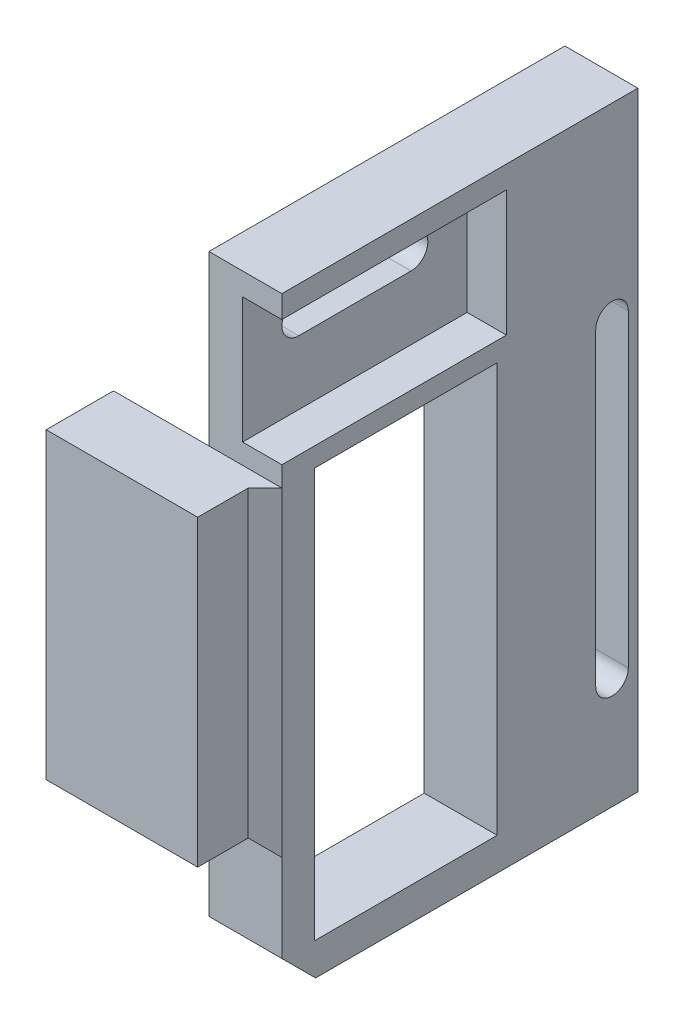
SolidWorks part; units mm, degrees
ref_plane "前视基准面" through (0, 0, 0) normal (0, 0, 1) x (1, 0, 0)
ref_plane "上视基准面" through (0, 0, 0) normal (0, 1, 0) x (1, 0, 0)
ref_plane "右视基准面" through (0, 0, 0) normal (1, 0, 0) x (0, 0, -1)
other "Configuration Table"
sketch "草图1" plane through (0, 0, 0) normal (1, 0, 0) x (0, 0, -1)
  line L0 (-13.55, 21.15) -> (13.55, 21.15)
  line L1 (-10.55, -18.15) -> (10.55, -18.15)
  line L2 (-10.55, -18.15) -> (-10.55, 18.15)
  line L3 (-10.55, 18.15) -> (10.55, 18.15)
  line L4 (10.55, -18.15) -> (10.55, 18.15)
  line L5 (-10.55, -18.15) -> (10.55, 18.15) construction
  line L6 (-10.55, 18.15) -> (10.55, -18.15) construction
  line L7 (13.55, -21.15) -> (13.55, 21.15)
  line L8 (-13.55, -21.15) -> (13.55, -21.15)
  line L9 (-13.55, -21.15) -> (-13.55, 21.15)
  point P0 (0, 0)
  dimension "D1" = 36.3
  dimension "D2" = 21.1
  dimension "D3" = 3
extrude "凸台-拉伸1" add sketch "草图1" along normal blind 6.5
chamfer "倒角1" distance 3 angle 45 4 edges at (3.25, -21.15, 13.55) (3.25, 21.15, 13.55) (3.25, 21.15, -13.55) (3.25, -21.15, -13.55)
sketch "草图2" plane through (0, 0, 0) normal (-1, 0, 0) x (0, 0, 1)
  line L0 (13.55, 18.15) -> (13.55, -18.15) construction
  line L1 (13.55, 12.15) -> (18.55, 12.15)
  line L2 (13.55, 12.15) -> (13.55, -12.15)
  line L3 (13.55, -12.15) -> (18.55, -12.15)
  line L4 (18.55, 12.15) -> (18.55, -12.15)
  line L5 (10.55, -18.15) -> (-10.55, -18.15) construction
  line L6 (-10.55, 18.15) -> (10.55, 18.15) construction
  circle A0 centre (16.05, 7.15) radius 1.475
  circle A1 centre (16.05, -7.15) radius 1.475
  dimension "D4" = 2.5
  dimension "D6" = 2.95
  dimension "D8" = 2.95
  dimension "D1" = 6
  dimension "D2" = 6
  dimension "D3" = 5
  dimension "D5" = 5
  dimension "D7" = 5
  dimension "D9" = 2.5
extrude "凸台-拉伸2" add sketch "草图2" along normal blind 8.7 and the other way blind 6.5
sketch "草图3" plane through (6.5, 0, 0) normal (1, 0, 0) x (0, 0, -1)
  line L0 (-13.55, 18.15) -> (-13.55, 12.15) construction
  line L1 (13.55, 18.15) -> (-13.55, 18.15)
  line L2 (13.55, 18.15) -> (13.55, 33.15)
  line L3 (13.55, 33.15) -> (-13.55, 33.15)
  line L4 (-13.55, 18.15) -> (-13.55, 33.15)
  dimension "D1" = 15
extrude "凸台-拉伸3" add sketch "草图3" against normal blind 6.5
sketch "草图4" plane through (0, 0, 0) normal (-1, 0, 0) x (0, 0, 1)
  line L0 (-10.55, 18.15) -> (10.55, 18.15) construction
  line L1 (-13.55, 33.15) -> (-31.1578, 33.15)
  line L2 (-13.55, 33.15) -> (-13.55, 18.15)
  line L3 (-13.55, 18.15) -> (-31.1578, 18.15)
  line L4 (-31.1578, 33.15) -> (-31.1578, 18.15)
extrude "凸台-拉伸4" add sketch "草图4" against normal blind 6.5
sketch "草图5" plane through (0, 0, 0) normal (-1, 0, 0) x (0, 0, 1)
  line L0 (13.55, 33.15) -> (13.55, 12.15) construction
  line L1 (13.55, 31.2141) -> (-6.45, 31.2141)
  line L2 (13.55, 31.2141) -> (13.55, 20.2141)
  line L3 (13.55, 20.2141) -> (-6.45, 20.2141)
  line L4 (-6.45, 31.2141) -> (-6.45, 20.2141)
  line L5 (10.55, -18.15) -> (-10.55, -18.15) construction
  line L6 (-10.55, 18.15) -> (-5.55, 18.15)
  line L7 (-10.55, 18.15) -> (-10.55, -18.15)
  line L8 (-10.55, -18.15) -> (-5.55, -18.15)
  line L9 (-5.55, 18.15) -> (-5.55, -18.15)
  line L10 (10.55, 18.15) -> (10.55, -18.15) construction
  dimension "D1" = 11
  dimension "D2" = 20
  dimension "D3" = 16.1
extrude "凸台-拉伸5" add sketch "草图5" against normal blind 6.5
sketch "草图6" plane through (0, 0, 0) normal (-1, 0, 0) x (0, 0, 1)
  line L0 (13.55, 33.15) -> (13.55, 12.15) construction
  line L1 (13.55, 31.15) -> (-6.45, 31.15)
  line L2 (13.55, 31.15) -> (13.55, 19.95)
  line L3 (13.55, 19.95) -> (-6.45, 19.95)
  line L4 (-6.45, 31.15) -> (-6.45, 19.95)
  line L5 (-31.1578, 33.15) -> (13.55, 33.15) construction
  dimension "D1" = 20
  dimension "D2" = 11.2
  dimension "D3" = 2
extrude "切除-拉伸5" cut sketch "草图6" against normal through all both
sketch "草图9" plane through (-8.7, 0, 0) normal (-1, 0, 0) x (0, 0, 1)
  line L4 (13.55, 12.15) -> (13.55, -12.15)
  line L5 (13.55, -12.15) -> (18.55, -12.15)
  line L6 (18.55, -12.15) -> (18.55, 12.15)
  line L7 (18.55, 12.15) -> (13.55, 12.15)
  line L8 (13.55, 12.15) -> (13.55, -12.15)
  line L9 (13.55, -12.15) -> (18.55, -12.15)
  line L10 (18.55, -12.15) -> (18.55, 12.15)
  line L11 (18.55, 12.15) -> (13.55, 12.15)
  dimension "D1" = 0
extrude "切除-拉伸6" cut sketch "草图9" against normal through all both
sketch "草图10" plane through (0, 0, 0) normal (-1, 0, 0) x (0, 0, 1)
  line L1 (13.55, 31.15) -> (-6.45, 31.15)
  line L2 (13.55, 31.15) -> (13.55, 19.95)
  line L3 (13.55, 19.95) -> (-6.45, 19.95)
  line L4 (-6.45, 31.15) -> (-6.45, 19.95)
extrude "凸台-拉伸6" add sketch "草图10" against normal blind 3
sketch "草图11" plane through (6.5, 0, 0) normal (1, 0, 0) x (0, 0, -1)
  line L0 (31.1578, 18.15) -> (13.55, 18.15) construction
  line L1 (31.1578, 33.15) -> (18.1578, 33.15)
  line L2 (31.1578, 33.15) -> (31.1578, 18.15)
  line L3 (31.1578, 18.15) -> (18.1578, 18.15)
  line L4 (18.1578, 33.15) -> (18.1578, 18.15)
  dimension "D1" = 13
extrude "切除-拉伸7" cut sketch "草图11" against normal through all both and the other way through all
sketch "草图13" plane through (0, 0, 0) normal (-1, 0, 0) x (0, 0, 1)
  line L0 (13.55, 33.15) -> (13.55, -18.15) construction
  line L1 (13.55, 18.15) -> (19.55, 18.15)
  line L2 (13.55, 18.15) -> (13.55, -8.85)
  line L3 (13.55, -8.85) -> (19.55, -8.85)
  line L4 (19.55, 18.15) -> (19.55, -8.85)
  line L5 (-5.55, 18.15) -> (10.55, 18.15) construction
  dimension "D1" = 6
  dimension "D2" = 27
  dimension "D3" = 0
extrude "凸台-拉伸7" add sketch "草图13" along normal blind 8.5 and the other way blind 5
chamfer "倒角2" distance 1.5 angle 45 2 edges at (5, 4.65, 13.55) (2.5, -8.85, 13.55)
sketch "草图14" plane through (0, 0, 0) normal (-1, 0, 0) x (0, 0, 1)
  line L0 (10.63, 18.23) -> (-5.63, 18.23)
  line L1 (-5.63, 18.23) -> (-5.63, -18.23)
  line L2 (-5.63, -18.23) -> (10.63, -18.23)
  line L3 (10.63, -18.23) -> (10.63, 18.23)
  line L4 (-5.55, 18.15) -> (-5.55, -18.15)
  line L5 (10.55, 18.15) -> (-5.55, 18.15)
  line L6 (10.55, -18.15) -> (10.55, 18.15)
  line L7 (-5.55, -18.15) -> (10.55, -18.15)
  line L8 (-5.55, 18.15) -> (-5.55, -18.15)
  line L9 (10.55, 18.15) -> (-5.55, 18.15)
  line L10 (10.55, -18.15) -> (10.55, 18.15)
  line L11 (-5.55, -18.15) -> (10.55, -18.15)
  dimension "D1" = 0
  dimension "D2" = 0.08
extrude "切除-拉伸8" cut sketch "草图14" against normal through all
sketch "草图15" plane through (6.5, 0, 0) normal (1, 0, 0) x (0, 0, -1)
  line L1 (18.1578, 18.15) -> (10.55, 18.15)
  line L2 (18.1578, 18.15) -> (18.1578, -21.15)
  line L3 (18.1578, -21.15) -> (10.55, -21.15)
  line L4 (10.55, 18.15) -> (10.55, -21.15)
extrude "凸台-拉伸8" add sketch "草图15" against normal blind 6
sketch "草图16" plane through (3, 0, 0) normal (1, 0, 0) x (0, 0, -1)
  line L0 (-8.55, 27.15) -> (1.45, 27.15) construction
  line L1 (-8.55, 28.65) -> (1.45, 28.65)
  line L2 (-8.55, 25.65) -> (1.45, 25.65)
  line L3 (6.45, 31.15) -> (6.45, 19.95) construction
  line L4 (-13.55, 31.15) -> (6.45, 31.15) construction
  arc A0 (-8.55, 28.65) -> (-8.55, 25.65) centre (-8.55, 27.15) ccw
  arc A1 (1.45, 25.65) -> (1.45, 28.65) centre (1.45, 27.15) ccw
  point P2 (-3.55, 27.15)
  dimension "D4" = 1.5
  dimension "D1" = 10
  dimension "D2" = 5
  dimension "D3" = 4
extrude "切除-拉伸9" cut sketch "草图16" against normal blind 6
sketch "草图17" plane through (0.5, 0, 0) normal (-1, 0, 0) x (0, 0, 1)
  line L5 (-13.55, -18.15) -> (-13.55, 18.15)
  line L6 (-13.55, 18.15) -> (-18.1578, 18.15)
  line L7 (-18.1578, 18.15) -> (-18.1578, -21.15)
  line L8 (-18.1578, -21.15) -> (-10.55, -21.15)
  line L9 (-10.55, -21.15) -> (-13.55, -18.15)
  line L10 (-13.55, -18.15) -> (-13.55, 18.15)
  line L11 (-13.55, 18.15) -> (-18.1578, 18.15)
  line L12 (-18.1578, 18.15) -> (-18.1578, -21.15)
  line L13 (-18.1578, -21.15) -> (-10.55, -21.15)
  line L14 (-10.55, -21.15) -> (-13.55, -18.15)
  dimension "D1" = 0
extrude "凸台-拉伸9" add sketch "草图17" along normal blind 0.5
sketch "草图18" plane through (0, 0, 0) normal (-1, 0, 0) x (0, 0, 1)
  line L0 (-15.8578, 11.85) -> (-15.8578, -11.15) construction
  line L1 (-14.4078, 11.85) -> (-14.4078, -11.15)
  line L2 (-17.3078, 11.85) -> (-17.3078, -11.15)
  line L3 (-18.1578, 33.15) -> (-18.1578, -21.15) construction
  line L5 (10.55, -21.15) -> (-18.1578, -21.15) construction
  arc A0 (-14.4078, 11.85) -> (-17.3078, 11.85) centre (-15.8578, 11.85) ccw
  arc A1 (-17.3078, -11.15) -> (-14.4078, -11.15) centre (-15.8578, -11.15) ccw
  point P2 (-15.8578, 0.35)
  dimension "D4" = 23
  dimension "D1" = 2.3
  dimension "D2" = 2.9
  dimension "D3" = 10
extrude "切除-拉伸10" cut sketch "草图18" against normal through all
sketch "草图19" plane through (6.5, 0, 0) normal (1, 0, 0) x (0, 0, -1)
  line L1 (14.4078, 11.85) -> (17.3078, 11.85)
  line L2 (14.4078, 11.85) -> (14.4078, 16.4)
  line L4 (17.3078, 11.85) -> (17.3078, 16.4)
  arc A0 (17.3078, 16.4) -> (14.4078, 16.4) centre (15.8578, 16.4) ccw
  dimension "D1" = 1.45
  dimension "D2" = 4.55
extrude "切除-拉伸11" cut sketch "草图19" against normal blind 10
